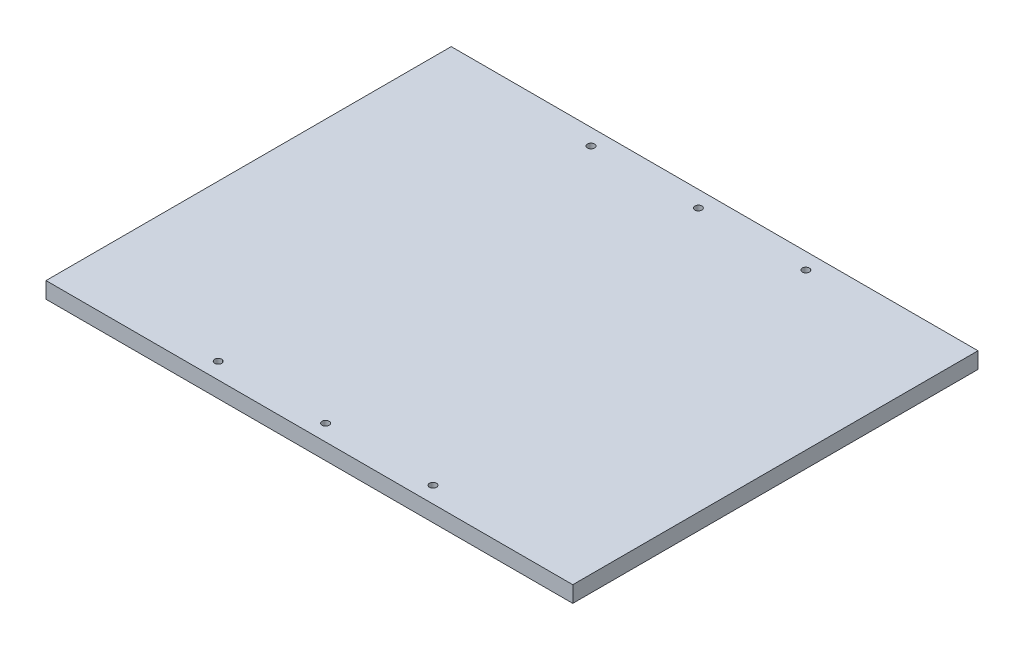
SolidWorks part; units mm, degrees
ref_plane "Ebene vorne" through (0, 0, 0) normal (0, 0, 1) x (1, 0, 0)
ref_plane "Ebene oben" through (0, 0, 0) normal (0, 1, 0) x (1, 0, 0)
ref_plane "Ebene rechts" through (0, 0, 0) normal (1, 0, 0) x (0, 0, -1)
sketch "Skizze1" plane through (0, 0, 0) normal (0, 1, 0) x (1, 0, 0)
  line L0 (-53, -92) -> (53, -92) construction
  line L1 (-130, -100) -> (130, -100)
  line L2 (-130, -100) -> (-130, 100)
  line L3 (-130, 100) -> (130, 100)
  line L4 (130, -100) -> (130, 100)
  line L5 (-130, -100) -> (130, 100) construction
  line L6 (-130, 100) -> (130, -100) construction
  line L7 (0, -100) -> (0, 100) construction
  line L8 (-130, 0) -> (130, 0) construction
  line L9 (-53, 92) -> (53, 92) construction
  circle A0 centre (-53, -92) radius 1.75
  circle A1 centre (53, -92) radius 1.75
  circle A2 centre (0, -92) radius 1.75
  circle A3 centre (0, 92) radius 1.75
  circle A4 centre (53, 92) radius 1.75
  circle A5 centre (-53, 92) radius 1.75
  point P0 (0, 0)
  point P15 (0, 0)
  point P18 (0, 0)
  dimension "D3" = 3.5
  dimension "D4" = 3.5
  dimension "D7" = 3.5
  dimension "D1" = 200
  dimension "D2" = 260
  dimension "D5" = 106
  dimension "D6" = 8
extrude "Aufsatz-Linear austragen1" add sketch "Skizze1" along normal blind 8
